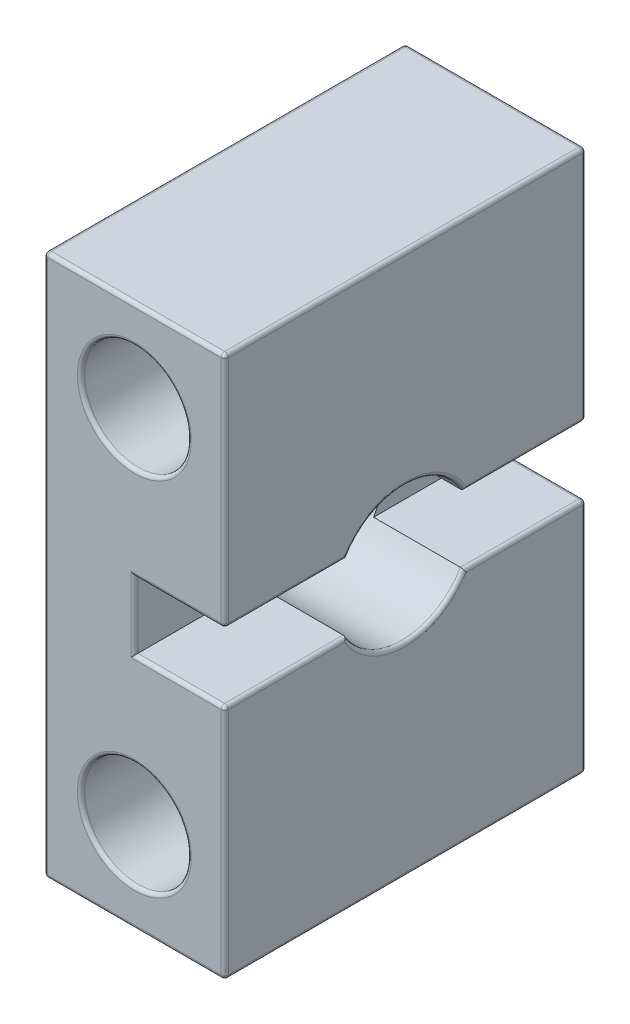
SolidWorks part; units mm, degrees
ref_plane "Front Plane" through (0, 0, 0) normal (0, 0, 1) x (1, 0, 0)
ref_plane "Top Plane" through (0, 0, 0) normal (0, 1, 0) x (1, 0, 0)
ref_plane "Right Plane" through (0, 0, 0) normal (1, 0, 0) x (0, 0, -1)
sketch "Sketch1" plane through (0, 0, 0) normal (0, 0, 1) x (1, 0, 0)
  line L1 (0, 0) -> (25.4, 0)
  line L2 (0, 0) -> (0, 76.2)
  line L3 (0, 76.2) -> (25.4, 76.2)
  line L4 (25.4, 0) -> (25.4, 76.2)
  dimension "D1" = 76.2
  dimension "D2" = 25.4
extrude "Extrude1" add sketch "Sketch1" along normal blind 50.8
hole_wizard "Ø15.0 (15) Diameter Hole1" positions "3DSketch1" profile "Sketch2" hole size "Ø15.0" standard "Ansi Metric" end condition up to next
sketch3d "3DSketch1"
  line L0 (25.4, 76.2, 50.8) -> (0, 76.2, 50.8) construction
  line L1 (0, 76.2, 50.8) -> (0, 0, 50.8) construction
  line L2 (0, 0, 50.8) -> (25.4, 0, 50.8) construction
  point P0 (12.7, 63.5, 50.8)
  point P2 (12.7, 12.7, 50.8)
  dimension "D1" = 12.7
  dimension "D2" = 12.7
  dimension "D3" = 12.7
  dimension "D4" = 12.7
sketch "Sketch2" plane through (12.7, 63.5, 50.8) normal (1, 0, 0) x (0, -1, 0)
  line L0 (0, 0) -> (0, 50.8)
  line L1 (0, 50.8) -> (7.5, 50.8)
  line L2 (7.5, 50.8) -> (7.5, 0)
  line L5 (7.5, 0) -> (0, 0)
  line L11 (0, -6.35) -> (0, 107.95) construction
  dimension "Thru Hole Dia." = 15
  dimension "Thru Hole Depth" = 50.8
sketch "Sketch9" plane through (0, 0, 0) normal (-1, 0, 0) x (0, 0, 1)
  line L0 (0, 76.2) -> (50.8, 0) construction
  circle A0 centre (25.4, 38.1) radius 9.525
  dimension "D1" = 19.05
extrude "Extrude3" cut sketch "Sketch9" against normal up to next
sketch "Sketch7" plane through (25.4, 0, 0) normal (1, 0, 0) x (0, 0, -1)
  line L0 (-50.8, 38.1) -> (0, 38.1) construction
  line L1 (-50.8, 0) -> (-50.8, 76.2) construction
  line L2 (0, 0) -> (0, 76.2) construction
  line L3 (-50.8, 33.3375) -> (0, 33.3375)
  line L4 (-50.8, 42.8625) -> (0, 42.8625)
  line L5 (0, 33.3375) -> (0, 42.8625)
  line L6 (-50.8, 33.3375) -> (-50.8, 42.8625)
  dimension "D1" = 4.7625
  dimension "D2" = 4.7625
extrude "Extrude2" cut sketch "Sketch7" against normal blind 12.7
fillet "Fillet1" radius 0.508 31 edges at (5.2, 12.7, 0) (5.2, 63.5, 0) (12.7, 0, 0) (19.05, 33.3375, 0) (12.7, 38.1, 0) (19.05, 42.8625, 0) (0, 0, 25.4) (0, 38.1, 0) (0, 76.2, 25.4) (12.7, 76.2, 0) (25.4, 0, 25.4) (25.4, 33.3375, 42.2244) (25.4, 33.3375, 8.5756) (25.4, 16.6687, 0) (25.4, 76.2, 25.4) (25.4, 59.5312, 0) (25.4, 42.8625, 8.5756) (25.4, 42.8625, 42.2244) (19.05, 33.3375, 50.8) (25.4, 16.6687, 50.8) (12.7, 0, 50.8) (0, 38.1, 50.8) (12.7, 76.2, 50.8) (25.4, 59.5312, 50.8) (19.05, 42.8625, 50.8) (12.7, 38.1, 50.8) (20.2, 12.7, 50.8) (20.2, 63.5, 50.8) (0, 38.1, 34.925) (25.4, 28.575, 25.4) (25.4, 47.625, 25.4)
